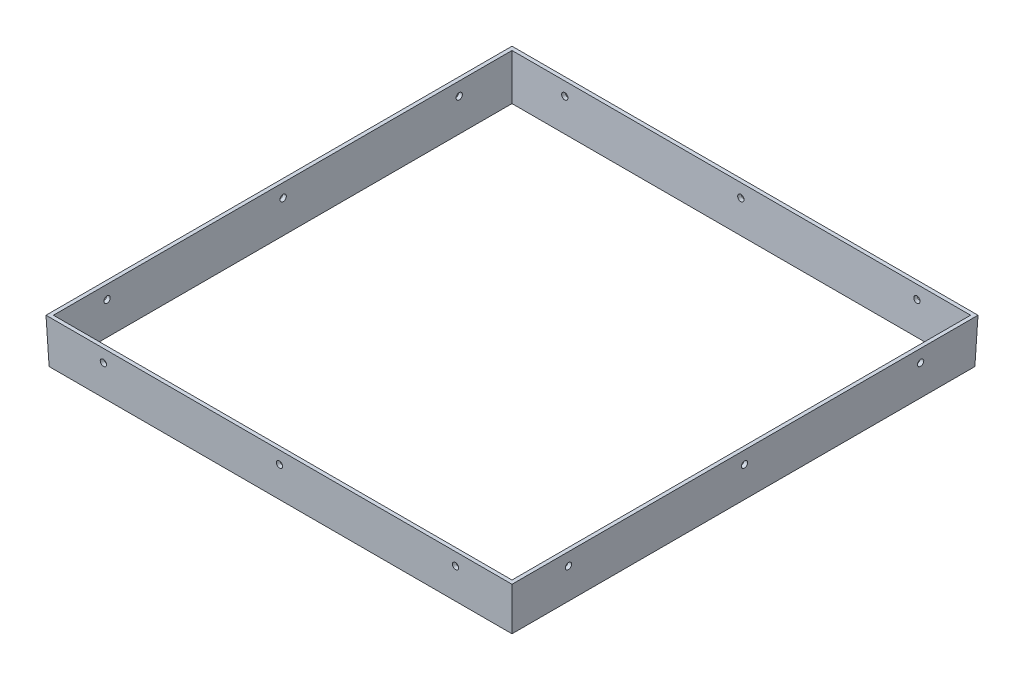
SolidWorks part; units mm, degrees
material "Alumina"
ref_plane "Front Plane" through (0, 0, 0) normal (0, 0, 1) x (1, 0, 0)
ref_plane "Top Plane" through (0, 0, 0) normal (0, 1, 0) x (1, 0, 0)
ref_plane "Right Plane" through (0, 0, 0) normal (1, 0, 0) x (0, 0, -1)
sketch "Sketch2" plane through (0, 0, 0) normal (0, 1, 0) x (1, 0, 0)
  line L0 (-124.88, -124.88) -> (124.88, -124.88)
  line L1 (-124.88, -124.88) -> (-124.88, 124.88)
  line L2 (-124.88, 124.88) -> (124.88, 124.88)
  line L3 (124.88, -124.88) -> (124.88, 124.88)
  line L4 (-124.88, -124.88) -> (124.88, 124.88) construction
  line L5 (-124.88, 124.88) -> (124.88, -124.88) construction
  point P0 (0, 0)
  dimension "D1" = 249.76
  dimension "D2" = 249.76
extrude "Boss-Extrude1" add sketch "Sketch2" along normal blind 24 draft 2 draft outward yes
shell "Shell1" thickness 2 removed face at (0, 0, 0) removed face at (0, 24, 0)
sketch "Sketch3" plane through (-124.7279, -4.3556, 0) normal (-0.9994, -0.0349, 0) x (0, 0, 1)
  line L0 (-125.7181, 28.3729) -> (125.7181, 28.3729) construction
  circle A0 centre (-95, 21.3729) radius 1.7
  circle A1 centre (0, 21.3729) radius 1.7
  circle A2 centre (95, 21.3729) radius 1.7
  point P6 (0, 0)
  point P10 (0, 0)
  point P11 (0, 0)
  dimension "D1" = 3.4
  dimension "D2" = 7
  dimension "D3" = 95
  dimension "D4" = 95
extrude "Cut-Extrude1" cut sketch "Sketch3" against normal blind 10 and the other way through all
mirror "Mirror1" about plane through (0, 0, 0) normal (1, 0, 0) of "Cut-Extrude1"
sketch "Sketch4" plane through (0, -4.3556, -124.7279) normal (0, -0.0349, -0.9994) x (-1, 0, 0)
  line L0 (-125.7181, 28.3729) -> (125.7181, 28.3729) construction
  circle A0 centre (-95, 21.3729) radius 1.7
  circle A1 centre (0, 21.3729) radius 1.7
  circle A2 centre (95, 21.3729) radius 1.7
  point P6 (0, 0)
  point P8 (0, 0)
  dimension "D4" = 3.4
  dimension "D1" = 7
  dimension "D2" = 95
  dimension "D3" = 95
extrude "Cut-Extrude2" cut sketch "Sketch4" against normal blind 10
mirror "Mirror2" about plane through (0, 0, 0) normal (0, 0, 1) of "Cut-Extrude2"
